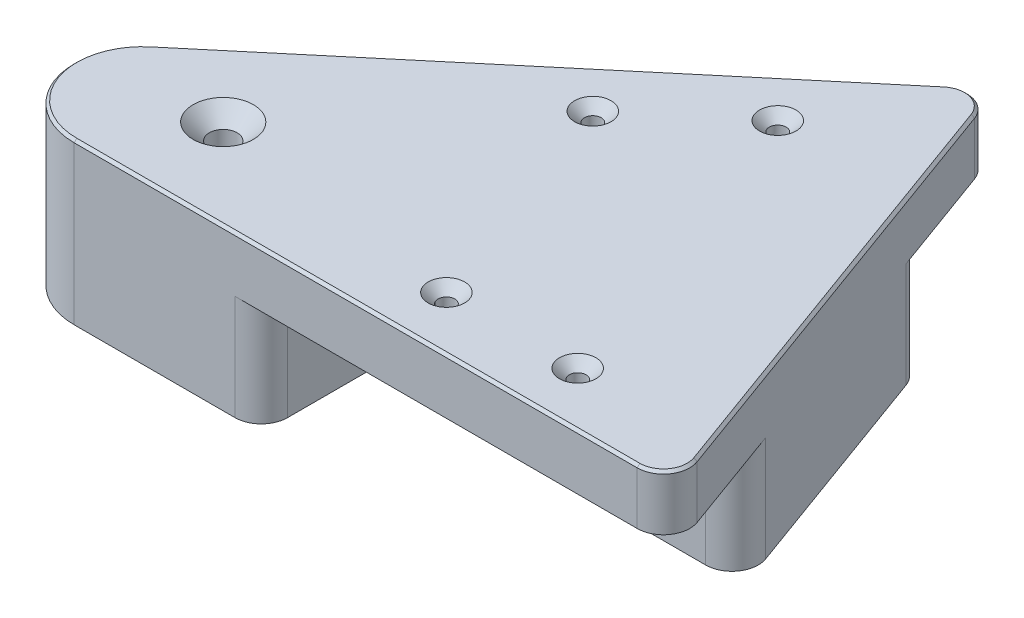
SolidWorks part; units mm, degrees
material "acero"
ref_plane "Alzado" through (0, 0, 0) normal (0, 0, 1) x (1, 0, 0)
ref_plane "Planta" through (0, 0, 0) normal (0, 1, 0) x (1, 0, 0)
ref_plane "Vista lateral" through (0, 0, 0) normal (1, 0, 0) x (0, 0, -1)
sketch "Sketch1" plane through (0, 0, 0) normal (0, 1, 0) x (1, 0, 0)
  line L0 (-75, 0) -> (75, 0)
  line L1 (-75, 0) -> (39.9067, 96.4181)
  line L2 (39.9067, 96.4181) -> (75, 0)
  line L3 (-3.6767, 20.5) -> (67.5386, 20.5)
  line L4 (-7.186, 30.1418) -> (47.3681, 75.9181)
  line L5 (-18.6767, 20.5) -> (53.0838, 80.7142) construction
  line L6 (-18.6767, 20.5) -> (75, 20.5) construction
  line L7 (-18.6767, 20.5) -> (-18.6767, 0) construction
  line L8 (-75, 0) -> (57.4533, 48.2091) construction
  line L9 (-34.1415, 3.9635) -> (-14.8778, 10.9749)
  line L10 (-34.1415, 3.9635) -> (-41.1529, 23.2272)
  line L11 (-41.1529, 23.2272) -> (-21.8892, 30.2386)
  line L12 (-14.8778, 10.9749) -> (-21.8892, 30.2386)
  line L13 (-34.1415, 3.9635) -> (-21.8892, 30.2386) construction
  line L14 (-18.6767, 20.5) -> (-31.8539, 36.2039) construction
  line L15 (43.6374, 86.1681) -> (-25.2653, 28.352) construction
  line L16 (-18.6767, 10.25) -> (71.2693, 10.25) construction
  line L17 (-3.6767, 20.5) -> (-3.6767, 0)
  line L18 (-41.1529, 23.2272) -> (-14.8778, 10.9749) construction
  line L24 (-7.186, 30.1418) -> (-20.3632, 45.8457)
  line L25 (-3.6767, 25.9596) -> (-20.3632, 45.8457) construction
  line L26 (-3.6767, 25.9596) -> (-3.6767, 0) construction
  circle A0 centre (-28.0154, 17.101) radius 1
  circle A1 centre (21.3053, 10.25) radius 1
  circle A2 centre (46.2873, 10.25) radius 1
  circle A3 centre (5.3627, 54.0519) radius 1
  circle A4 centre (24.5, 70.11) radius 1
  point P9 (-28.0154, 17.101)
  dimension "D9" = 2
  dimension "D1" = 150
  dimension "D2" = 150
  dimension "D7" = 10.25
  dimension "D8" = 10.25
  dimension "D10" = 24.982
  dimension "D13" = 24.982
  dimension "D3" = 40
  dimension "D11" = 74.946
  dimension "D12" = 24.982
  dimension "D14" = 24.982
  dimension "D5" = 20.5
  dimension "D6" = 50
  dimension "D4" = 20.5
  dimension "D16" = 15
extrude "Main Body" add sketch "Sketch1" along normal blind 10.5 contours L7 L14 L1 L0 | L3 L7 L0 L2 A2 A1 | L14 L4 L2 L1 A4 A3 | L4 L3 L2 | L9 L12 L11 L10 A0 region at (8.8772, 0, -30.5288) region at (33.8274, 0, -10.0792) region at (14.8454, 0, -62.2318) region at (-37.298, 0, -13.7224)
extrude "Profile Stops" add sketch "Sketch1<3>" against normal blind 20 contours L7 L14 L1 L0 region at (8.8772, 0, -30.5288)
sketch "Sketch1<3>" plane through (0, 0, 0) normal (0, 1, 0) x (1, 0, 0) same geometry as "Sketch1"
hole_wizard "CSK for M3 Hex Socket Countersunk Head Screw1" positions "3DSketch1" profile "Sketch4" countersink size "M3" standard "DIN" end condition up to next
sketch3d "3DSketch1"
  line L0 (24.5, 10.5, -70.11) -> (24.5, 0, -70.11) construction
  line L1 (5.3627, 10.5, -54.0519) -> (5.3627, 0, -54.0519) construction
  line L2 (46.2873, 10.5, -10.25) -> (46.2873, 0, -10.25) construction
  line L3 (21.3053, 10.5, -10.25) -> (21.3053, 0, -10.25) construction
  point P0 (24.5, 10.5, -70.11)
  point P4 (5.3627, 10.5, -54.0519)
  point P8 (46.2873, 10.5, -10.25)
  point P12 (21.3053, 10.5, -10.25)
sketch "Sketch4" plane through (24.5, 10.5, -70.11) normal (1, 0, 0) x (0, 0, 1)
  line L0 (0, 0) -> (0, 30.5)
  line L1 (0, 30.5) -> (1.6, 30.5)
  line L2 (1.6, 30.5) -> (1.6, 1.87)
  line L3 (1.6, 1.87) -> (3.47, 0)
  line L5 (3.47, 0) -> (0, 0)
  line L6 (-1.6, 1.87) -> (-3.47, 0) construction
  line L11 (0, -6.35) -> (0, 107.95) construction
  dimension "Thru Hole Dia." = 3.2
  dimension "Thru Hole Depth" = 30.5
  dimension "Near C'Sink Dia." = 6.94
  dimension "Near C'Sink Angle" = 90
hole_wizard "CSK for M5 Hex Socket Countersunk Head Screw1" positions "3DSketch2" profile "Sketch5" countersink size "M5" standard "DIN" end condition up to next
sketch3d "3DSketch2"
  line L1 (-28.0154, 10.5, -17.101) -> (-28.0154, 0, -17.101) construction
  point P0 (-28.0154, 10.5, -17.101)
  point P4 (38.0512, 10.5, -41.1473)
  point P5 (-28.0154, 10.5, -17.101)
sketch "Sketch5" plane through (-28.0154, 10.5, -17.101) normal (1, 0, 0) x (0, 0, 1)
  line L0 (0, 0) -> (0, 30.5)
  line L1 (0, 30.5) -> (2.65, 30.5)
  line L2 (2.65, 30.5) -> (2.65, 3.085)
  line L3 (2.65, 3.085) -> (5.735, 0)
  line L5 (5.735, 0) -> (0, 0)
  line L6 (-2.65, 3.085) -> (-5.735, 0) construction
  line L11 (0, -6.35) -> (0, 107.95) construction
  dimension "Thru Hole Dia." = 5.3
  dimension "Thru Hole Depth" = 30.5
  dimension "Near C'Sink Dia." = 11.47
  dimension "Near C'Sink Angle" = 90
fillet "Fillet1" radius 5 2 edges at (-3.6767, -10, 0) (-20.3632, -10, -45.8457)
fillet "Fillet3" radius 5 4 edges at (75, 5.25, 0) (67.5386, -10, -20.5) (47.3681, -10, -75.9181) (39.9067, 5.25, -96.4181)
fillet "Fillet4" radius 13 1 edges at (-75, -4.75, 0)
draft "Draft1" type of draft neutral plane draft angle 0.5 faces to draft 4 face at (-31.5211, -10, -26.7329) face at (-18.3835, -10, -20.6067) face at (-37.6472, -10, -13.5953) face at (-24.5097, -10, -7.4692) neutral plane through (0, 0, 0) neutral plane normal (0, -1, 0) parameters "D1"=0.5
chamfer "Chamfer1" distance 0.5 angle 45 6 edges at (57.4533, 10.5, -48.2091) (38.9446, 10.5, -92.8276) (71.955, 10.5, -2.1321) (-6.6012, 10.5, -57.3934) (14.2882, 10.5, 0) (-51.4988, 10.5, -8.5537)
equation "\"D2@Sketch1\"=\"D1@Sketch1\""
equation "\"D7@Sketch1\"=\"D4@Sketch1\"/2"
equation "\"D8@Sketch1\"=\"D7@Sketch1\""
equation "\"D10@Sketch1\"=\"D11@Sketch1\"/3"
equation "\"D13@Sketch1\"=\"D10@Sketch1\""
equation "\"D12@Sketch1\"=\"D10@Sketch1\""
equation "\"D14@Sketch1\"=\"D13@Sketch1\""
